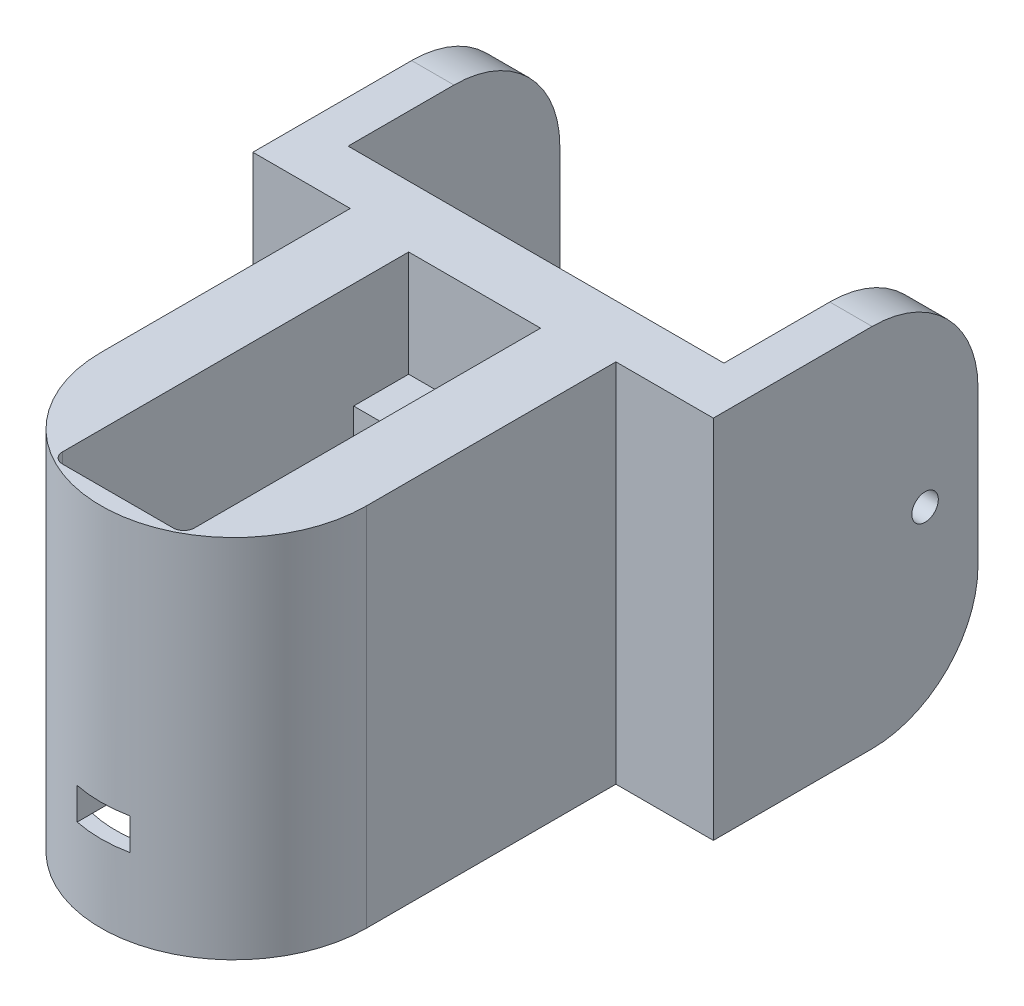
SolidWorks part; units mm, degrees
ref_plane "Front Plane" through (0, 0, 0) normal (0, 0, 1) x (1, 0, 0)
ref_plane "Top Plane" through (0, 0, 0) normal (0, 1, 0) x (1, 0, 0)
ref_plane "Right Plane" through (0, 0, 0) normal (1, 0, 0) x (0, 0, -1)
sketch "Sketch4" plane through (0, 0, 0) normal (0, 0, 1) x (1, 0, 0)
  line L1 (-6.23, -9.975) -> (6.23, -9.975)
  line L2 (-6.23, -9.975) -> (-6.23, 7.275)
  line L3 (-6.23, 7.275) -> (6.23, 7.275)
  line L4 (6.23, -9.975) -> (6.23, 7.275)
  point P4 (0, 7.275)
  dimension "D1" = 12.46
  dimension "D2" = 17.25
  dimension "D3" = 9.975
extrude "Boss-Extrude3" add sketch "Sketch4" along normal blind 6
sketch "Sketch8" plane through (0, -9.975, 0) normal (0, -1, 0) x (-1, 0, 0)
  circle A0 centre (0, -23.55) radius 12.5468
  circle A1 centre (0, -23.55) radius 11.15
  dimension "D1" = 22.3
  dimension "D2" = 23.55
extrude "Boss-Extrude6" add sketch "Sketch8" along normal blind 7.3 and the other way up to surface (17.25 mm away) other way up to face at (0, 7.275, 3)
sketch "Sketch5" plane through (0, 7.275, 0) normal (0, 1, 0) x (1, 0, 0)
  line L8 (12.5468, -23.55) -> (12.5468, 0)
  line L9 (12.5468, 0) -> (6.23, 0)
  line L10 (-12.5468, -23.55) -> (-12.5468, 0)
  line L11 (-12.5468, 0) -> (-6.23, 0)
  line L12 (-6.23, 0) -> (-6.23, -29.7)
  line L14 (6.23, -29.7) -> (6.23, 0)
  line L15 (-6.23, -29.7) -> (6.23, -29.7)
  line L16 (6.23, -6) -> (-6.23, -6) construction
  circle A0 centre (0, -23.55) radius 12.5468 construction
  arc A1 (-12.5468, -23.55) -> (12.5468, -23.55) centre (0, -23.55) ccw
  dimension "D1" = 23.7
  dimension "D2" = 23.55
extrude "Boss-Extrude4" add sketch "Sketch5" against normal up to surface (17.25 mm away) up to face at (0, -9.975, 3)
sketch "Sketch6" plane through (0, 7.275, 0) normal (0, 1, 0) x (1, 0, 0)
  line L0 (6.23, -6) -> (-6.23, -6) construction
  line L3 (6.23, -29.7) -> (-6.23, -29.7) construction
  circle A0 centre (0, -3.5) radius 2
  circle A1 centre (0, -32.2) radius 2
  dimension "D1" = 4
  dimension "D3" = 4
  dimension "D2" = 2.5
  dimension "D4" = 2.5
extrude "Cut-Extrude1" cut sketch "Sketch6" against normal blind 5
chamfer "Chamfer1" distance 0.5 angle 60 2 edges at (0, 7.275, 5.5) (0, 7.275, 34.2) first distance on face at (0, 7.275, 5.5)
sketch "Sketch10" plane through (0, 7.275, 0) normal (0, 1, 0) x (1, 0, 0)
  line L1 (-6.23, -6) -> (6.23, -6)
  line L2 (-6.23, -6) -> (-6.23, -29.7)
  line L3 (-6.23, -29.7) -> (6.23, -29.7)
  line L4 (6.23, -6) -> (6.23, -29.7)
extrude "Cut-Extrude3" cut sketch "Sketch10" against normal up to surface (17.25 mm away) up to face at (0, -9.975, 10.3399)
ref_plane "Plane1" through (0, 0, 36.0968) normal (0, 0, 1) x (1, 0, 0)
sketch "Sketch11" plane through (0, 0, 36.0968) normal (0, 0, 1) x (1, 0, 0)
  line L0 (-11.15, -9.975) -> (11.15, -9.975) construction
  line L1 (-2.5, -6.975) -> (2.5, -6.975)
  line L2 (-2.5, -6.975) -> (-2.5, -9.975)
  line L3 (-2.5, -9.975) -> (2.5, -9.975)
  line L4 (2.5, -6.975) -> (2.5, -9.975)
  point P4 (0, -6.975)
  dimension "D1" = 0
  dimension "D2" = 5
  dimension "D3" = 3
extrude "Cut-Extrude4" cut sketch "Sketch11" against normal up to next
sketch "Sketch13" plane through (0, -17.275, 0) normal (0, -1, 0) x (1, 0, 0)
  line L0 (-12.5468, 23.55) -> (-12.5468, 0)
  line L1 (-12.5468, 0) -> (12.5468, 0)
  line L2 (12.5468, 0) -> (12.5468, 23.55)
  arc A0 (-12.5468, 23.55) -> (12.5468, 23.55) centre (0, 23.55) ccw
  point P3 (0, 0)
extrude "Boss-Extrude7" add sketch "Sketch13" against normal up to surface (7.3 mm away) up to face at (0, -9.975, 10.3399)
sketch "Sketch15" plane through (0, 7.275, 0) normal (0, 1, 0) x (1, 0, 0)
  line L0 (-12.5468, 0) -> (12.5468, 0)
  line L1 (12.5468, 0) -> (12.5468, -23.55)
  line L2 (-12.5468, 0) -> (-12.5468, -23.55)
  line L3 (6.23, -6) -> (6.23, -29.7) construction
  line L4 (-6.23, -0.8) -> (6.23, -0.8)
  line L5 (-6.23, -0.8) -> (-6.23, -33.5)
  line L6 (-5.23, -34.5) -> (5.23, -34.5)
  line L7 (6.23, -0.8) -> (6.23, -33.5)
  arc A0 (-12.5468, -23.55) -> (12.5468, -23.55) centre (0, -23.55) ccw
  circle A1 centre (0, -3.5) radius 2 construction
  arc A2 (5.23, -34.5) -> (6.23, -33.5) centre (5.23, -33.5) ccw
  arc A3 (-6.23, -33.5) -> (-5.23, -34.5) centre (-5.23, -33.5) ccw
  point P15 (0, -0.8)
  dimension "D1" = 0.8
  dimension "D3" = 1
  dimension "D2" = 2.7
  dimension "D4" = 0
  dimension "D5" = 34.5
extrude "Boss-Extrude9" add sketch "Sketch15" along normal blind 10
sketch "Sketch17" plane through (0, 17.275, 0) normal (0, 1, 0) x (1, 0, 0)
  line L0 (21.75, 25) -> (21.75, 0)
  line L1 (21.75, 0) -> (-21.75, 0)
  line L2 (-21.75, 0) -> (-21.75, 25)
  line L3 (-21.75, 25) -> (-17.75, 25)
  line L4 (-17.75, 25) -> (-17.75, 5)
  line L5 (-17.75, 5) -> (17.75, 5)
  line L6 (17.75, 5) -> (17.75, 25)
  line L7 (17.75, 25) -> (21.75, 25)
  point P2 (0, 5)
  point P10 (0, 0)
  dimension "D1" = 4
  dimension "D2" = 35.5
  dimension "D3" = 0
  dimension "D4" = 25
  dimension "D5" = 5
extrude "Boss-Extrude10" add sketch "Sketch17" against normal up to surface (34.55 mm away) up to face at (0, -17.275, 14.9117)
sketch "Sketch18" plane through (17.75, 0, 0) normal (-1, 0, 0) x (0, 0, 1)
  line L0 (-25, -17.275) -> (-25, 17.275) construction
  line L1 (-25, 6.2191) -> (-5, 6.2191)
  line L2 (-25, 6.2191) -> (-25, -6.2191)
  line L3 (-25, -6.2191) -> (-5, -6.2191)
  line L4 (-5, 6.2191) -> (-5, -6.2191)
  line L5 (-5, -17.275) -> (-5, 17.275) construction
  point P6 (-25, 0)
  point P7 (-25, 0)
  dimension "D1" = 0
extrude "Cut-Extrude5" cut sketch "Sketch18" against normal blind 2
sketch "Sketch19" plane through (19.75, 0, 0) normal (-1, 0, 0) x (0, 0, 1)
  line L0 (-25, -17.275) -> (-25, 17.275) construction
  circle A0 centre (-20, 0) radius 1.25
  dimension "D1" = 2.5
  dimension "D2" = 5
extrude "Cut-Extrude6" cut sketch "Sketch19" against normal through all both and the other way through all
fillet "Fillet1" radius 10 4 edges at (19.75, -17.275, -25) (19.75, 17.275, -25) (-19.75, 17.275, -25) (-19.75, -17.275, -25)
ref_plane "Plane2" through (0, 0, 0) normal (1, 0, 0) x (0, 0, -1)
ref_plane "Plane3" through (0, 0, 0) normal (0, -1, 0) x (-1, 0, 0)
